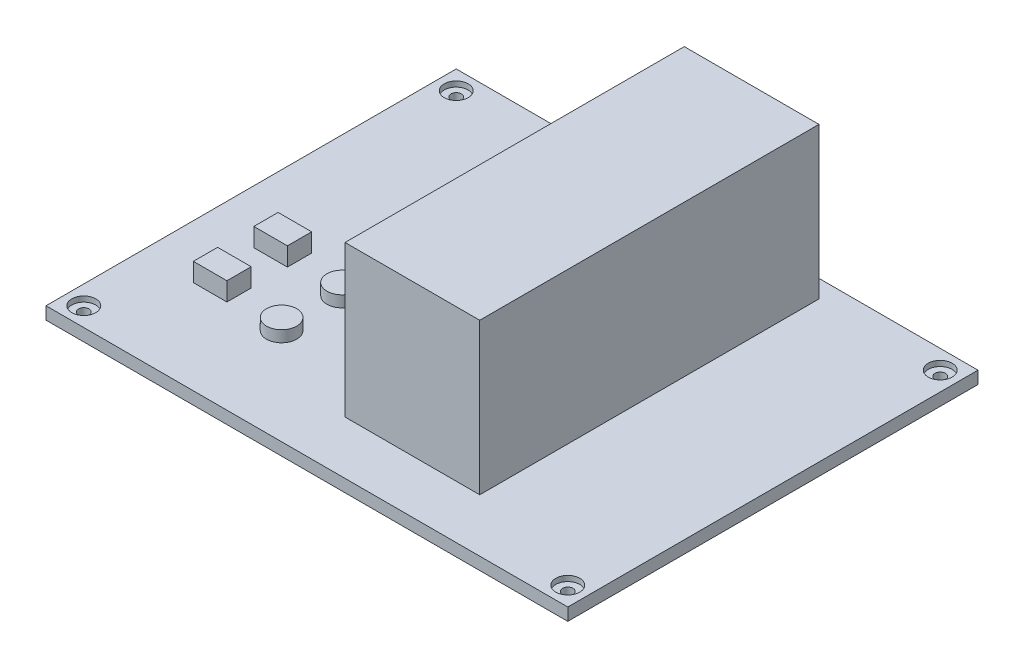
SolidWorks part; units mm, degrees
ref_plane "Front Plane" through (0, 0, 0) normal (0, 0, 1) x (1, 0, 0)
ref_plane "Top Plane" through (0, 0, 0) normal (0, 1, 0) x (1, 0, 0)
ref_plane "Right Plane" through (0, 0, 0) normal (1, 0, 0) x (0, 0, -1)
sketch "Sketch1" plane through (0, 0, 0) normal (0, 1, 0) x (1, 0, 0)
  line L1 (-34.515, -27.135) -> (34.515, -27.135)
  line L2 (-34.515, -27.135) -> (-34.515, 27.135)
  line L3 (-34.515, 27.135) -> (34.515, 27.135)
  line L4 (34.515, -27.135) -> (34.515, 27.135)
  line L5 (-34.515, -27.135) -> (34.515, 27.135) construction
  line L6 (-34.515, 27.135) -> (34.515, -27.135) construction
  point P0 (0, 0)
  dimension "D1" = 69.03
  dimension "D2" = 54.27
extrude "Boss-Extrude1" add sketch "Sketch1" along normal blind 1.65
sketch "Sketch2" plane through (0, 1.65, 0) normal (0, 1, 0) x (1, 0, 0)
  line L0 (-34.515, 27.135) -> (-34.515, -27.135) construction
  line L2 (-34.515, -27.135) -> (34.515, -27.135) construction
  line L5 (34.515, 27.135) -> (-34.515, 27.135) construction
  circle A0 centre (-16.095, -14.385) radius 2
  circle A1 centre (-16.095, -6.385) radius 2
  dimension "D1" = 18.42
  dimension "D3" = 8
  dimension "D2" = 12.75
extrude "Boss-Extrude2" add sketch "Sketch2" along normal blind 1.5
sketch "Sketch3" plane through (0, 1.65, 0) normal (0, 1, 0) x (1, 0, 0)
  line L0 (-34.515, -27.135) -> (34.515, -27.135) construction
  line L1 (-27.415, -11.53) -> (-22.975, -11.53)
  line L2 (-27.415, -11.53) -> (-27.415, -14.74)
  line L3 (-27.415, -14.74) -> (-22.975, -14.74)
  line L4 (-22.975, -11.53) -> (-22.975, -14.74)
  line L5 (-27.415, -11.53) -> (-22.975, -14.74) construction
  line L6 (-27.415, -14.74) -> (-22.975, -11.53) construction
  line L7 (-34.515, 27.135) -> (-34.515, -27.135) construction
  line L9 (-27.415, -3.53) -> (-22.975, -3.53)
  line L10 (-27.415, -3.53) -> (-27.415, -6.74)
  line L11 (-27.415, -6.74) -> (-22.975, -6.74)
  line L12 (-22.975, -3.53) -> (-22.975, -6.74)
  line L13 (-27.415, -3.53) -> (-22.975, -6.74) construction
  line L14 (-27.415, -6.74) -> (-22.975, -3.53) construction
  point P0 (-25.195, -13.135)
  point P10 (-25.195, -5.135)
  dimension "D1" = 14
  dimension "D2" = 9.32
  dimension "D3" = 4.44
  dimension "D4" = 3.21
  dimension "D5" = 3.21
  dimension "D6" = 4.44
  dimension "D7" = 8
extrude "Boss-Extrude3" add sketch "Sketch3" along normal blind 2.44
sketch "Sketch4" plane through (0, 1.65, 0) normal (0, 1, 0) x (1, 0, 0)
  line L0 (34.515, -27.135) -> (34.515, 27.135) construction
  line L1 (-1.985, 24.775) -> (15.835, 24.775)
  line L2 (-1.985, 24.775) -> (-1.985, -20.105)
  line L3 (-1.985, -20.105) -> (15.835, -20.105)
  line L4 (15.835, 24.775) -> (15.835, -20.105)
  line L5 (-34.515, -27.135) -> (34.515, -27.135) construction
  dimension "D1" = 17.82
  dimension "D2" = 44.88
  dimension "D3" = 18.68
  dimension "D4" = 7.03
extrude "Boss-Extrude4" add sketch "Sketch4" along normal blind 20
hole_wizard "CBORE for #00 Binding Head Machine Screw1" positions "Sketch5" profile "Sketch6" counterbore size "#00" standard "ANSI Inch" end condition through all
sketch "Sketch5" plane through (18.6603, 1.65, 81.8304) normal (0, 1, 0) x (0, 0, 1)
  point P0 (-106.4654, -50.6753)
  point P1 (-57.1954, -50.6753)
  point P2 (-57.1954, 13.3547)
  point P3 (-106.4654, 13.3547)
  point P12 (-55.8951, 15.8547)
sketch "Sketch6" plane through (-32.015, 1.65, -24.635) normal (1, 0, 0) x (0, 0, 1)
  line L0 (0, 0) -> (0, 1.65)
  line L1 (0, 1.65) -> (0.6985, 1.65)
  line L2 (0.6985, 1.65) -> (0.6985, 0.7112)
  line L3 (0.6985, 0.7112) -> (1.5875, 0.7112)
  line L4 (1.5875, 0.7112) -> (1.5875, 0)
  line L5 (1.5875, 0) -> (0, 0)
  line L6 (0, -6.35) -> (0, 107.95) construction
  dimension "Thru Hole Dia." = 1.397
  dimension "Thru Hole Depth" = 1.65
  dimension "C'Bore Dia." = 3.175
  dimension "C'Bore Depth" = 0.7112
